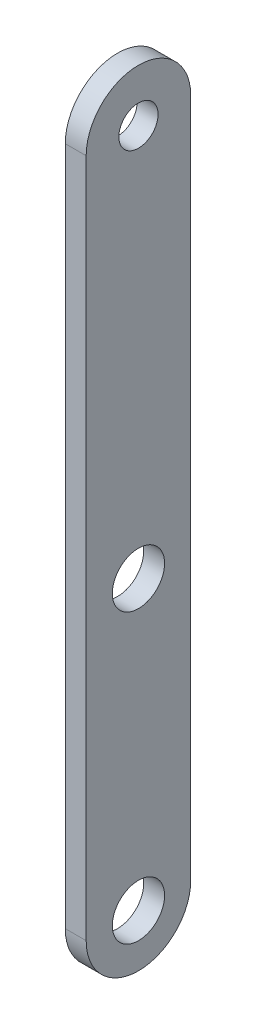
SolidWorks part; units mm, degrees
ref_plane "Front Plane" through (0, 0, 0) normal (0, 0, 1) x (1, 0, 0)
ref_plane "Top Plane" through (0, 0, 0) normal (0, 1, 0) x (1, 0, 0)
ref_plane "Right Plane" through (0, 0, 0) normal (1, 0, 0) x (0, 0, -1)
sketch "Sketch2" plane through (0, 0, 0) normal (1, 0, 0) x (0, 0, -1)
  line L0 (-20, 0) -> (20, 0) construction
  line L1 (-20, 0) -> (-20, -260)
  line L2 (20, 0) -> (20, -260)
  line L3 (0, 0) -> (0, 7.5) construction
  line L11 (-20, -260) -> (20, -260) construction
  line L12 (0, 0) -> (0, -150) construction
  circle A0 centre (0, 0) radius 7.5
  arc A1 (-20, 0) -> (20, 0) centre (0, 0) cw
  circle A2 centre (0, -150) radius 10
  arc A3 (-20, -260) -> (20, -260) centre (0, -260) ccw
  circle A4 centre (0, -260) radius 10
  point P11 (0, 1.423)
  point P17 (-20, 35.5)
  dimension "D1" = 15
  dimension "D7" = 20
  dimension "D8" = 20
  dimension "D2" = 40
  dimension "D3" = 260
  dimension "D6" = 150
extrude "Boss-Extrude1" add sketch "Sketch2" along normal blind 4 and the other way blind 4 contours L1 A3 L2 A1 A0 A2 region at (0, -127.7744, 0)
